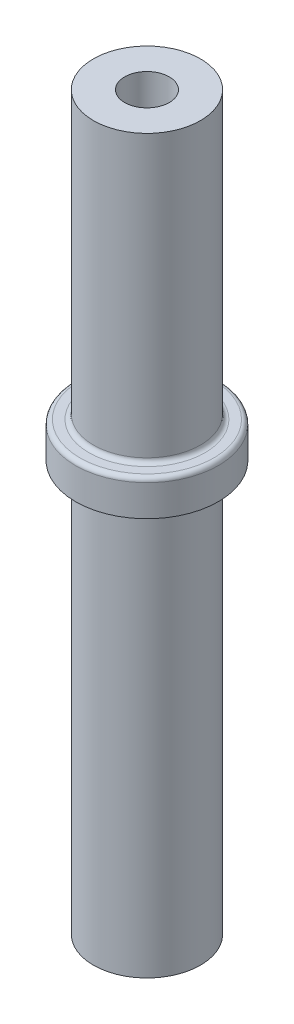
SolidWorks part; units mm, degrees
material "6061-T6 (SS)"
ref_plane "Front Plane" through (0, 0, 0) normal (0, 0, 1) x (1, 0, 0)
ref_plane "Top Plane" through (0, 0, 0) normal (0, 1, 0) x (1, 0, 0)
ref_plane "Right Plane" through (0, 0, 0) normal (1, 0, 0) x (0, 0, -1)
sketch "Sketch1" plane through (0, 0, 0) normal (0, 1, 0) x (1, 0, 0)
  circle A0 centre (0, 0) radius 3
  circle A1 centre (0, 0) radius 2 construction
  dimension "D1" = 6
  dimension "D2" = 4
extrude "Boss-Extrude1" add sketch "Sketch1" along normal blind 20.5 and the other way blind 20.5
sketch "Sketch2" plane through (0, 20.5, 0) normal (0, 1, 0) x (1, 0, 0)
  point P0 (0, 0)
hole_wizard "M3x0.5 Tapped Hole1" positions "Sketch4" profile "Sketch5" tap size "M3x0.5" standard "ANSI Metric"
sketch "Sketch4" plane through (0, 20.5, 0) normal (0, 1, 0) x (1, 0, 0)
  point P0 (0, 0)
sketch "Sketch5" plane through (0, 20.5, 0) normal (1, 0, 0) x (0, 0, 1)
  line L0 (0, 0) -> (0, 8.7511)
  line L1 (0, 8.7511) -> (1.25, 8)
  line L2 (1.25, 8) -> (1.25, 0)
  line L5 (1.25, 0) -> (0, 0)
  line L10 (0, 8.7511) -> (-1.25, 8) construction
  line L11 (0, -6.35) -> (0, 107.95) construction
  dimension "Tap Drill Dia." = 2.5
  dimension "Tap Drill Depth" = 8
  dimension "Drill Angle" = 118
cosmetic thread "Hole Thread1" parameters "D1"=6, "D2"=3
ref_plane "Plane1" through (0, 2.5, 0) normal (0, 1, 0) x (1, 0, 0)
sketch "Sketch6" plane through (0, 2.5, 0) normal (0, 1, 0) x (1, 0, 0)
  circle A0 centre (0, 0) radius 4
  dimension "D1" = 8
extrude "Boss-Extrude2" add sketch "Sketch6" along normal blind 2
mirror "Mirror1" about plane through (0, 0, 0) normal (0, 1, 0) of "M3x0.5 Tapped Hole1"
fillet "Fillet1" radius 0.25 2 edges at (0, 4.5, 4) (0, 4.5, 3)
